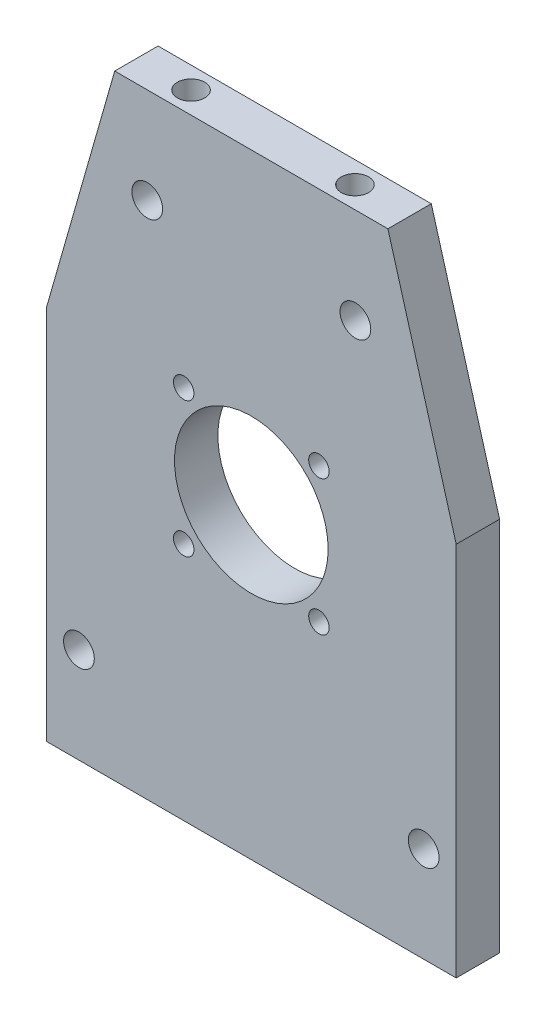
SolidWorks part; units mm, degrees
material "6061 Alloy"
ref_plane "Front Plane" through (0, 0, 0) normal (0, 0, 1) x (1, 0, 0)
ref_plane "Top Plane" through (0, 0, 0) normal (0, 1, 0) x (1, 0, 0)
ref_plane "Right Plane" through (0, 0, 0) normal (1, 0, 0) x (0, 0, -1)
sketch "Sketch1" plane through (0, 0, 0) normal (0, 0, 1) x (1, 0, 0)
  line L0 (-20, 45) -> (20, 45)
  line L5 (-30, -45) -> (30, -45)
  line L6 (0, 45) -> (0, -45) construction
  line L7 (-20, 45) -> (-30, 10)
  line L8 (-30, 10) -> (-30, -45)
  line L9 (30, 10) -> (30, -45)
  line L10 (20, 45) -> (30, 10)
  dimension "D1" = 90
  dimension "D2" = 60
  dimension "D3" = 40
  dimension "D4" = 55
extrude "1/4" add sketch "Sketch1" along normal mid plane 6.35
sketch "Sketch3" plane through (0, 0, 0) normal (0, 0, 1) x (1, 0, 0)
  circle A0 centre (0, 0) radius 11.25
  dimension "D1" = 22.5
extrude "Cut-Extrude2" cut sketch "Sketch3" along normal up to surface (3.175 mm away) and the other way blind 8 up to face at (0, 3.3333, 3.175)
sketch "Sketch2" plane through (0, 0, 3.175) normal (0, 0, 1) x (1, 0, 0)
  line L0 (-9.8995, 9.8995) -> (0, 0) construction
  line L1 (20, 45) -> (-20, 45) construction
  circle A0 centre (0, 0) radius 14 construction
  circle A1 centre (-9.8995, 9.8995) radius 1.5
  circle A2 centre (9.8995, 9.8995) radius 1.5
  circle A3 centre (9.8995, -9.8995) radius 1.5
  circle A4 centre (-9.8995, -9.8995) radius 1.5
  point P16 (0, 0)
  dimension "D1" = 28
  dimension "D3" = 3
  dimension "D2" = 45
  dimension "D4" = 4
extrude "M3_DRILL" cut sketch "Sketch2" against normal up to surface (6.35 mm away) up to face at (11.25, 0, -3.175)
sketch "Sketch4" plane through (0, 45, 0) normal (0, 1, 0) x (1, 0, 0)
  line L0 (0, -3.175) -> (0, 3.175) construction
  line L1 (0, 0) -> (-12, 0) construction
  line L2 (20, -3.175) -> (-20, -3.175) construction
  line L3 (20, 3.175) -> (-20, 3.175) construction
  circle A0 centre (-12, 0) radius 2
  circle A1 centre (12, 0) radius 2
  dimension "D2" = 4
  dimension "D1" = 12
extrude "M4_DRILL" cut sketch "Sketch4" against normal blind 8
sketch "Sketch5" plane through (0, -45, 0) normal (0, -1, 0) x (-1, 0, 0)
  line L0 (0, -3.175) -> (0, 3.175) construction
  line L2 (0, 0) -> (-20, 0) construction
  line L3 (30, -3.175) -> (-30, -3.175) construction
  line L4 (30, 3.175) -> (-30, 3.175) construction
  circle A0 centre (-20, 0) radius 2
  circle A1 centre (20, 0) radius 2
  circle A2 centre (0, 0) radius 2
  dimension "D1" = 4
  dimension "D2" = 20
extrude "M4_DRILL2" cut sketch "Sketch5" against normal blind 8
sketch "Sketch6" plane through (0, 0, 3.175) normal (0, 0, 1) x (1, 0, 0)
  line L2 (0, 0) -> (0, -45.222) construction
  line L4 (20, 45) -> (-20, 45) construction
  line L5 (-30, -45) -> (30, -45) construction
  line L6 (-30, 10) -> (-30, -45) construction
  circle A0 centre (-25.2375, -31) radius 2.25
  circle A1 centre (25.2375, -31) radius 2.25
  circle A2 centre (-15.2375, 31) radius 2.25
  circle A3 centre (15.2375, 31) radius 2.25
  dimension "D1" = 4.5
  dimension "D6" = 4.5
  dimension "D2" = 14
  dimension "D3" = 4.7625
  dimension "D4" = 14
  dimension "D5" = 4.7625
extrude "M4_through" cut sketch "Sketch6" against normal up to surface (6.35 mm away) up to face at (-8.3995, -9.8995, -3.175)
